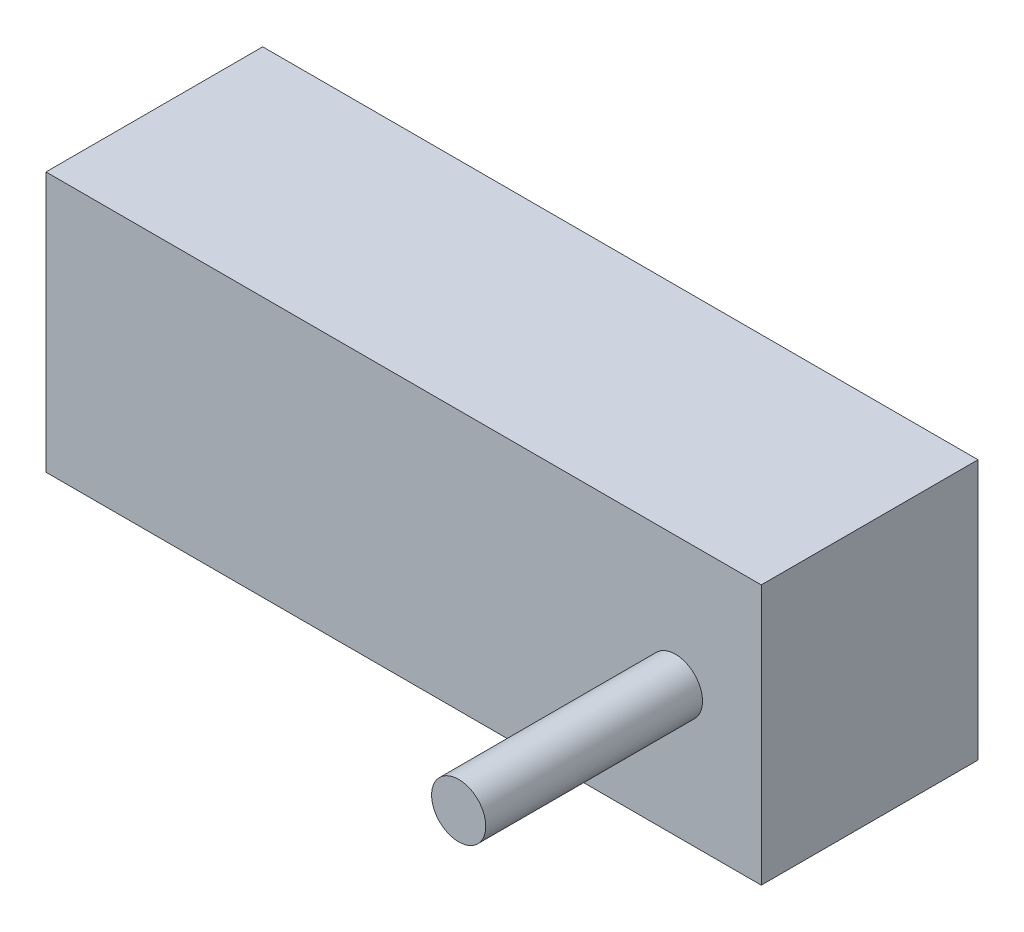
SolidWorks part; units mm, degrees
ref_plane "Front Plane" through (0, 0, 0) normal (0, 0, 1) x (1, 0, 0)
ref_plane "Top Plane" through (0, 0, 0) normal (0, 1, 0) x (1, 0, 0)
ref_plane "Right Plane" through (0, 0, 0) normal (1, 0, 0) x (0, 0, -1)
sketch "Sketch1" plane through (0, 0, 0) normal (0, 0, 1) x (1, 0, 0)
  line L1 (0, 0) -> (33, 0)
  line L2 (0, 0) -> (0, 12)
  line L3 (0, 12) -> (33, 12)
  line L4 (33, 0) -> (33, 12)
  circle A0 centre (29.04, 6) radius 1.25
  dimension "D3" = 2.5
  dimension "D5" = 6
  dimension "D1" = 12
  dimension "D2" = 33
  dimension "D4" = 3.96
extrude "Boss-Extrude2" add sketch "Sketch1" along normal blind 20 contours A0
extrude "Boss-Extrude3" add sketch "Sketch1<5>" along normal blind 10
sketch "Sketch1<5>" plane through (0, 0, 0) normal (0, 0, 1) x (1, 0, 0) same geometry as "Sketch1"
